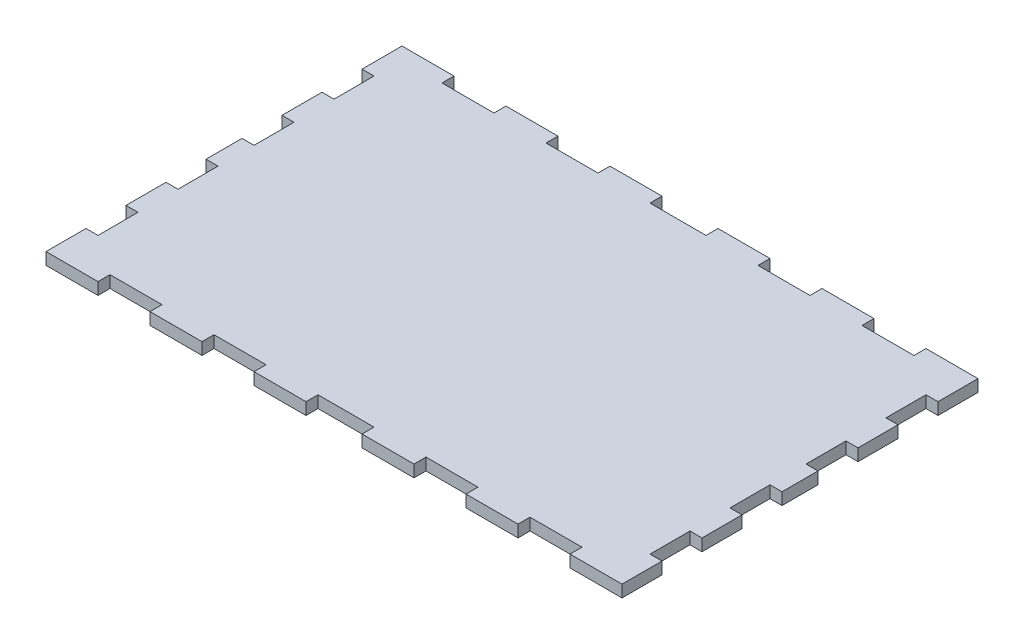
SolidWorks part; units mm, degrees
ref_plane "Front Plane" through (0, 0, 0) normal (0, 0, 1) x (1, 0, 0)
ref_plane "Top Plane" through (0, 0, 0) normal (0, 1, 0) x (1, 0, 0)
ref_plane "Right Plane" through (0, 0, 0) normal (1, 0, 0) x (0, 0, -1)
sketch "Sketch1" plane through (0, 0, 0) normal (0, 1, 0) x (1, 0, 0)
  line L0 (26, 89) -> (39, 89)
  line L1 (0, 0) -> (13, 0)
  line L2 (0, 0) -> (0, 10)
  line L3 (0, 89) -> (13, 89)
  line L4 (144, 0) -> (144, 10)
  line L5 (0, 79) -> (0, 89)
  line L6 (13, 0) -> (13, 3)
  line L7 (13, 3) -> (26, 3)
  line L8 (26, 0) -> (26, 3)
  line L9 (144, 79) -> (141, 79)
  line L10 (39, 0) -> (39, 3)
  line L11 (39, 3) -> (52, 3)
  line L12 (52, 0) -> (52, 3)
  line L14 (65, 0) -> (65, 3)
  line L15 (65, 3) -> (79, 3)
  line L16 (79, 0) -> (79, 3)
  line L17 (144, 69) -> (141, 69)
  line L18 (92, 0) -> (92, 3)
  line L19 (92, 3) -> (105, 3)
  line L20 (105, 0) -> (105, 3)
  line L21 (141, 79) -> (141, 69)
  line L22 (118, 0) -> (118, 3)
  line L23 (118, 3) -> (131, 3)
  line L24 (131, 0) -> (131, 3)
  line L25 (52, 0) -> (65, 0)
  line L26 (13, 89) -> (13, 86)
  line L27 (13, 86) -> (26, 86)
  line L28 (26, 89) -> (26, 86)
  line L29 (79, 0) -> (92, 0)
  line L30 (39, 89) -> (39, 86)
  line L31 (39, 86) -> (52, 86)
  line L32 (52, 89) -> (52, 86)
  line L33 (105, 0) -> (118, 0)
  line L34 (65, 89) -> (65, 86)
  line L35 (65, 86) -> (79, 86)
  line L36 (79, 89) -> (79, 86)
  line L37 (131, 0) -> (144, 0)
  line L38 (92, 89) -> (92, 86)
  line L39 (92, 86) -> (105, 86)
  line L40 (105, 89) -> (105, 86)
  line L41 (144, 59) -> (141, 59)
  line L42 (118, 89) -> (118, 86)
  line L43 (118, 86) -> (131, 86)
  line L44 (131, 89) -> (131, 86)
  line L45 (52, 89) -> (65, 89)
  line L46 (79, 89) -> (92, 89)
  line L47 (105, 89) -> (118, 89)
  line L48 (131, 89) -> (144, 89)
  line L49 (26, 0) -> (39, 0)
  line L51 (144, 49) -> (141, 49)
  line L52 (141, 59) -> (141, 49)
  line L53 (144, 40) -> (141, 40)
  line L55 (144, 30) -> (141, 30)
  line L56 (141, 40) -> (141, 30)
  line L57 (144, 20) -> (141, 20)
  line L59 (144, 10) -> (141, 10)
  line L60 (141, 20) -> (141, 10)
  line L61 (0, 79) -> (3, 79)
  line L62 (144, 59) -> (144, 69)
  line L63 (0, 69) -> (3, 69)
  line L64 (3, 79) -> (3, 69)
  line L65 (0, 59) -> (3, 59)
  line L66 (144, 40) -> (144, 49)
  line L67 (0, 49) -> (3, 49)
  line L68 (3, 59) -> (3, 49)
  line L69 (0, 40) -> (3, 40)
  line L70 (144, 20) -> (144, 30)
  line L71 (0, 30) -> (3, 30)
  line L72 (3, 40) -> (3, 30)
  line L73 (0, 20) -> (3, 20)
  line L75 (0, 10) -> (3, 10)
  line L76 (3, 20) -> (3, 10)
  line L77 (0, 59) -> (0, 69)
  line L78 (0, 40) -> (0, 49)
  line L79 (0, 20) -> (0, 30)
  line L80 (144, 79) -> (144, 89)
  dimension "D1" = 144
  dimension "D2" = 89
  dimension "D3" = 13
  dimension "D4" = 13
  dimension "D5" = 13
  dimension "D6" = 13
  dimension "D7" = 13
  dimension "D8" = 14
  dimension "D9" = 13
  dimension "D10" = 13
  dimension "D11" = 13
  dimension "D12" = 13
  dimension "D13" = 3
  dimension "D14" = 14
  dimension "D15" = 13
  dimension "D16" = 13
  dimension "D17" = 13
  dimension "D18" = 13
  dimension "D19" = 13
  dimension "D20" = 13
  dimension "D21" = 13
  dimension "D22" = 13
  dimension "D23" = 13
  dimension "D24" = 3
  dimension "D25" = 9
  dimension "D26" = 10
  dimension "D27" = 10
  dimension "D28" = 10
  dimension "D29" = 10
  dimension "D30" = 10
  dimension "D31" = 10
  dimension "D32" = 10
  dimension "D33" = 3
  dimension "D34" = 9
  dimension "D35" = 10
  dimension "D36" = 10
  dimension "D37" = 10
  dimension "D38" = 10
  dimension "D39" = 10
  dimension "D40" = 10
  dimension "D41" = 10
  dimension "D42" = 3
extrude "Boss-Extrude1" add sketch "Sketch1" along normal blind 3
